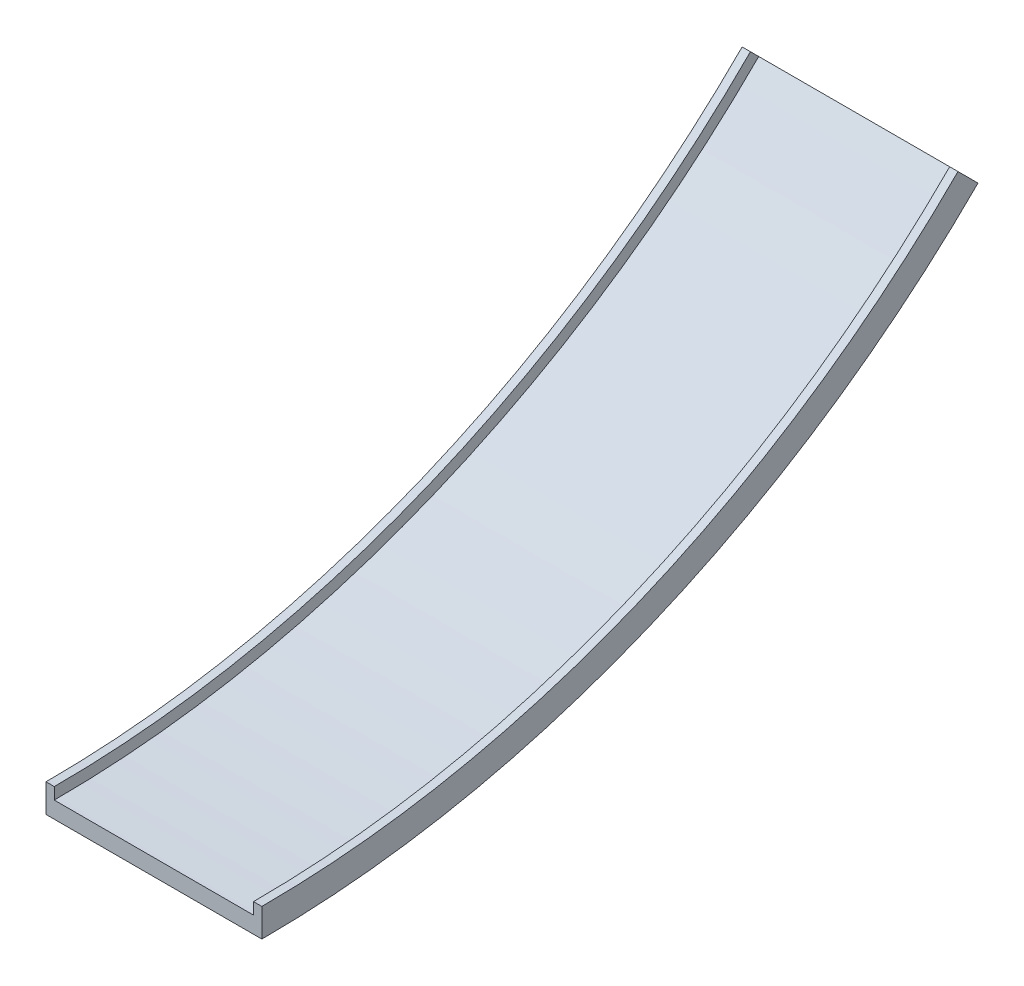
SolidWorks part; units mm, degrees
ref_plane "Front Plane" through (0, 0, 0) normal (0, 0, 1) x (1, 0, 0)
ref_plane "Top Plane" through (0, 0, 0) normal (0, 1, 0) x (1, 0, 0)
ref_plane "Right Plane" through (0, 0, 0) normal (1, 0, 0) x (0, 0, -1)
sketch "Sketch1" plane through (0, 0, 0) normal (0, 0, 1) x (1, 0, 0)
  line L0 (0, 0) -> (25, 0)
  line L1 (25, 0) -> (25, -35.2361)
  line L2 (25, -35.2361) -> (625, -35.2361)
  line L3 (625, -35.2361) -> (625, 0)
  line L4 (625, 0) -> (650, 0)
  line L5 (650, 0) -> (650, -85.2361)
  line L6 (650, -85.2361) -> (0, -85.2361)
  line L7 (0, -85.2361) -> (0, 0)
  line L8 (0, 2964.7639) -> (650, 2964.7639)
  dimension "D1" = 25
  dimension "D2" = 35.2361
  dimension "D3" = 650
  dimension "D4" = 50
  dimension "D5" = 3000
revolve "Revolve1" add sketch "Sketch1" angle 45 about L8 region at (325, -58.0446, 0)
